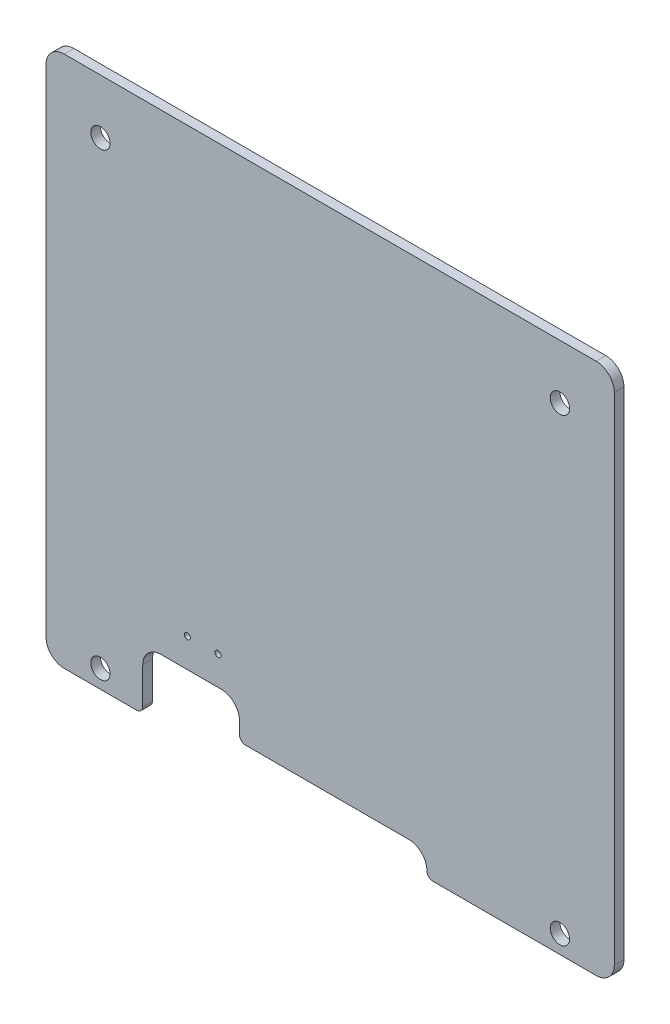
SolidWorks part; units mm, degrees
ref_plane "Front Plane" through (0, 0, 0) normal (0, 0, 1) x (1, 0, 0)
ref_plane "Top Plane" through (0, 0, 0) normal (0, 1, 0) x (1, 0, 0)
ref_plane "Right Plane" through (0, 0, 0) normal (1, 0, 0) x (0, 0, -1)
sketch "Sketch1" plane through (0, 0, 0) normal (0, 0, 1) x (1, 0, 0)
  line L0 (-55.5653, 7.9519) -> (-55.5653, 13.9519)
  line L1 (-87.5653, 88.9519) -> (-87.5653, 6.9519)
  line L2 (6.4347, 88.9519) -> (6.4347, 6.9519)
  line L3 (-84.5653, 91.9519) -> (3.4347, 91.9519)
  line L4 (-55.5653, 13.9519) -> (-71.5653, 13.9519)
  line L5 (-71.5653, 13.9519) -> (-71.5653, 3.9519)
  line L6 (6.4347, 6.9519) -> (6.4347, 88.9519) construction
  line L7 (-84.5653, 3.9519) -> (-71.5653, 3.9519)
  line L13 (-55.5653, 7.9519) -> (-24.5653, 7.9519)
  line L14 (-24.5653, 7.9519) -> (-24.5653, 3.9519)
  line L15 (-24.5653, 3.9519) -> (3.4347, 3.9519)
  arc A0 (3.4347, 3.9519) -> (6.4347, 6.9519) centre (3.4347, 6.9519) ccw
  arc A1 (-84.5653, 3.9519) -> (-87.5653, 6.9519) centre (-84.5653, 6.9519) cw
  arc A2 (-84.5653, 91.9519) -> (-87.5653, 88.9519) centre (-84.5653, 88.9519) ccw
  arc A3 (3.4347, 91.9519) -> (6.4347, 88.9519) centre (3.4347, 88.9519) cw
  circle A4 centre (-59.1053, 18.7519) radius 0.5
  circle A5 centre (-64.1853, 18.7519) radius 0.5
  dimension "D5" = 3
  dimension "D7" = 16
  dimension "D6" = 3
  dimension "D9" = 88
  dimension "D10" = 3
  dimension "D13" = 31
  dimension "D14" = 88
  dimension "D4" = 3
  dimension "D2" = 88
  dimension "D3" = 94
  dimension "D8" = 31
  dimension "D11" = 10
  dimension "D12" = 4
extrude "Boss-Extrude1" add sketch "Sketch1" along normal blind 1.6
hole_wizard "Ø3.2 (3.2) Diameter Hole3" positions "Sketch7" profile "Sketch6" hole size "Ø3.2" standard "Ansi Metric" end condition up to next
sketch "Sketch7" plane through (0, 0, 0) normal (0, 0, -1) x (-1, 0, 0)
  line L2 (-6.4347, 6.9519) -> (-6.4347, 88.9519) construction
  line L4 (87.5653, 47.9519) -> (-6.4347, 47.9519) construction
  line L5 (87.5653, 88.9519) -> (87.5653, 6.9519) construction
  line L6 (40.5653, 91.9519) -> (40.5653, 3.9519) construction
  line L7 (-3.4347, 91.9519) -> (84.5653, 91.9519) construction
  point P6 (78.5653, 6.9519)
  point P9 (78.5653, 82.9519)
  point P12 (2.5653, 82.9519)
  point P15 (2.5653, 6.9519)
  dimension "D1" = 35
  dimension "D2" = 38
  dimension "D3" = 38
  dimension "D4" = 35
  dimension "D5" = 41
  dimension "D6" = 38
  dimension "D7" = 38
sketch "Sketch6" plane through (-78.5653, 6.9519, 0) normal (1, 0, 0) x (0, 1, 0)
  line L0 (0, 0) -> (0, 1.6)
  line L1 (0, 1.6) -> (1.6, 1.6)
  line L2 (1.6, 1.6) -> (1.6, 0)
  line L5 (1.6, 0) -> (0, 0)
  line L11 (0, -6.35) -> (0, 107.95) construction
  dimension "Thru Hole Dia." = 3.2
  dimension "Thru Hole Depth" = 1.6
fillet "Fillet1" radius 3 3 edges at (-55.5653, 13.9519, 0.8) (-71.5653, 13.9519, 0.8) (-24.5653, 7.9519, 0.8)
fillet "Fillet2" radius 1 3 edges at (-24.5653, 3.9519, 0.8) (-71.5653, 3.9519, 0.8) (-55.5653, 7.9519, 0.8)
